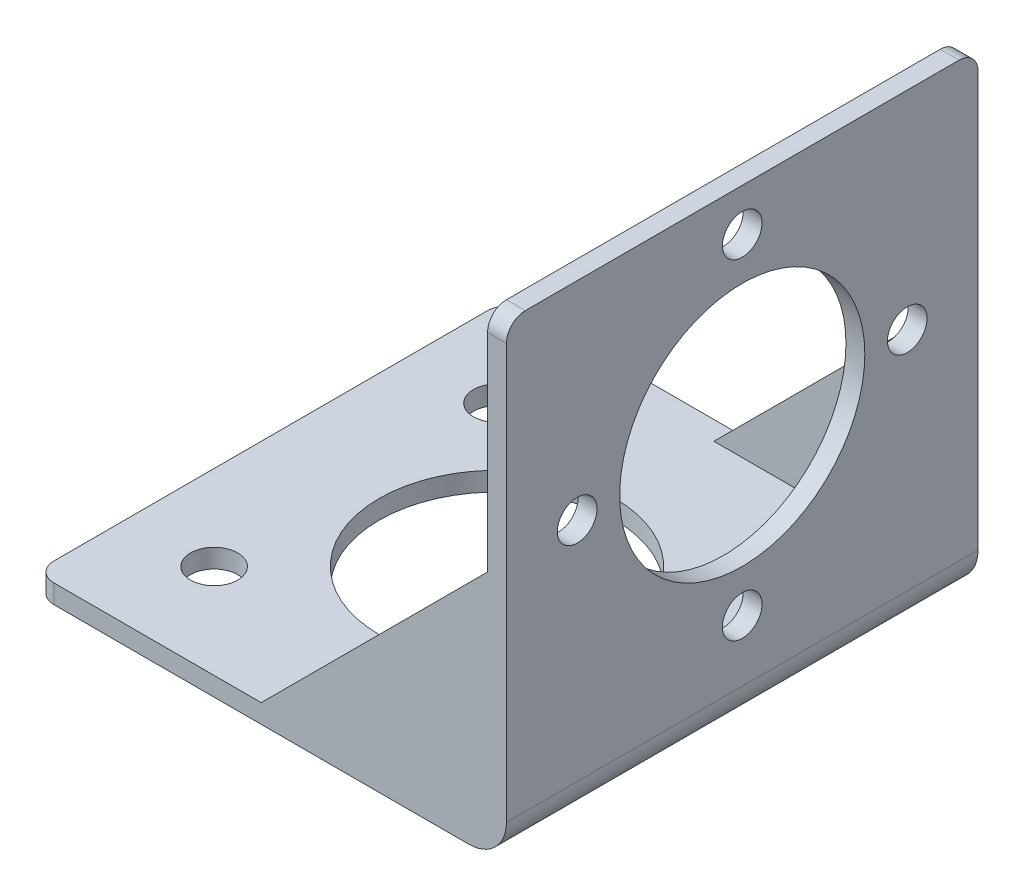
SolidWorks part; units mm, degrees
material "AISI 304"
ref_plane "前视基准面" through (0, 0, 0) normal (0, 0, 1) x (1, 0, 0)
ref_plane "上视基准面" through (0, 0, 0) normal (0, 1, 0) x (1, 0, 0)
ref_plane "右视基准面" through (0, 0, 0) normal (1, 0, 0) x (0, 0, -1)
sketch "草图1" plane through (0, 0, 0) normal (0, 0, 1) x (1, 0, 0)
  line L0 (0, 0) -> (46, 0)
  line L1 (50, 4) -> (50, 50)
  line L2 (50, 50) -> (48, 50)
  line L3 (48, 50) -> (48, 4)
  line L4 (46, 2) -> (0, 2)
  line L5 (0, 2) -> (0, 0)
  arc A0 (48, 4) -> (46, 2) centre (46, 4) cw
  arc A1 (46, 0) -> (50, 4) centre (46, 4) ccw
  point P11 (50, 0)
  point P12 (0, 0)
  dimension "D3" = 2
  dimension "D1" = 50
  dimension "D2" = 2
extrude "凸台-拉伸1" add sketch "草图1" along normal blind 50
sketch "草图2" plane through (50, 0, 0) normal (1, 0, 0) x (0, 0, -1)
  line L0 (-25, 50) -> (-25, 28) construction
  line L1 (-50, 50) -> (0, 50) construction
  circle A0 centre (-25, 28) radius 13
  circle A1 centre (-25, 28) radius 17.5 construction
  circle A2 centre (-25, 45.5) radius 2.1
  circle A3 centre (-7.5, 28) radius 2.1
  circle A4 centre (-25, 10.5) radius 2.1
  circle A5 centre (-42.5, 28) radius 2.1
  dimension "D1" = 35
  dimension "D2" = 4.2
  dimension "D3" = 26
  dimension "D4" = 28
extrude "切除-拉伸1" cut sketch "草图2" against normal blind 50
fillet "圆角1" radius 2 4 edges at (0, 1, 50) (0, 1, 0) (49, 50, 0) (49, 50, 50)
sketch "草图4" plane through (0, 0, 0) normal (0, -1, 0) x (1, 0, 0)
  line L0 (0, 25) -> (24, 25) construction
  line L1 (0, 48) -> (0, 2) construction
  line L2 (50, 50) -> (50, 0) construction
  line L3 (9, 40) -> (39, 40) construction
  line L4 (9, 40) -> (9, 10) construction
  line L5 (9, 10) -> (39, 10) construction
  line L6 (39, 40) -> (39, 10) construction
  line L7 (9, 40) -> (39, 10) construction
  line L8 (9, 10) -> (39, 40) construction
  circle A0 centre (24, 25) radius 12.5
  circle A1 centre (39, 10) radius 2.5
  circle A2 centre (9, 10) radius 2.5
  circle A3 centre (9, 40) radius 2.5
  circle A4 centre (39, 40) radius 2.5
  dimension "D1" = 5
  dimension "D2" = 25
  dimension "D4" = 26
  dimension "D3" = 30
extrude "切除-拉伸2" cut sketch "草图4" against normal blind 50
sketch "草图5" plane through (0, 0, 0) normal (0, 0, -1) x (-1, 0, 0)
  line L0 (-48, 26) -> (-24, 2)
  line L1 (-48, 48) -> (-48, 4) construction
  line L2 (-46, 2) -> (-2, 2) construction
  line L3 (-24, 2) -> (-48.8284, 1.1716)
  line L4 (-48.8284, 1.1716) -> (-48, 26)
  line L5 (-50, 4) -> (-50, 48) construction
  arc A0 (-50, 4) -> (-46, 0) centre (-46, 4) ccw construction
  dimension "D1" = 26
extrude "凸台-拉伸2" add sketch "草图5" against normal blind 2
extrude "凸台-拉伸3" add sketch "草图5<2>" along normal blind 2 from surface starting at face at (36.6553, 13.3447, 50)
sketch "草图5<2>" plane through (0, 0, 0) normal (0, 0, -1) x (-1, 0, 0) same geometry as "草图5"
